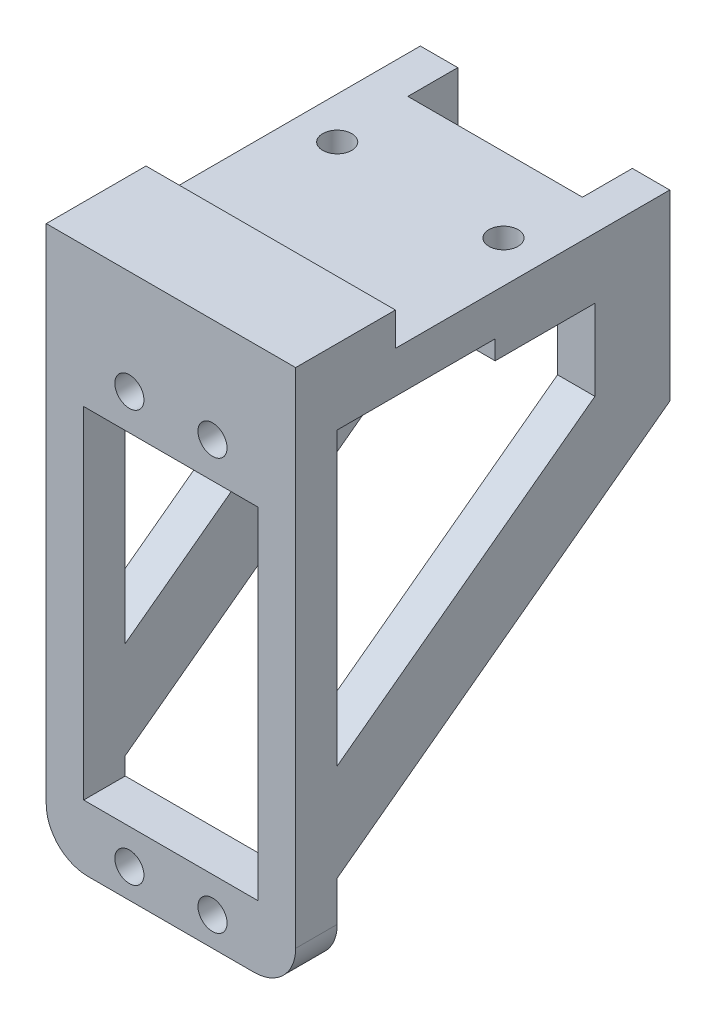
SolidWorks part; units mm, degrees
ref_plane "正面(Front)" through (0, 0, 0) normal (0, 0, 1) x (1, 0, 0)
ref_plane "平面(Top)" through (0, 0, 0) normal (0, 1, 0) x (1, 0, 0)
ref_plane "右側面(Right)" through (0, 0, 0) normal (1, 0, 0) x (0, 0, -1)
sketch "ｽｹｯﾁ1" plane through (0, 0, 0) normal (0, 0, 1) x (1, 0, 0)
  line L1 (0, 0) -> (30, 0)
  line L2 (0, 0) -> (0, 61.5)
  line L3 (0, 61.5) -> (30, 61.5)
  line L4 (30, 0) -> (30, 61.5)
  dimension "D1" = 30
  dimension "D2" = 61.5
extrude "ﾎﾞｽ - 押し出し1" add sketch "ｽｹｯﾁ1" along normal blind 5
sketch "ｽｹｯﾁ2" plane through (0, 0, 5) normal (0, 0, 1) x (1, 0, 0)
  line L0 (15, 0) -> (15, 69.5246) construction
  line L1 (0, 0) -> (30, 0) construction
  line L2 (15, 28.2) -> (37.391, 28.2) construction
  line L3 (4.5, 48.7) -> (25.5, 48.7)
  line L4 (4.5, 48.7) -> (4.5, 7.7)
  line L5 (4.5, 7.7) -> (25.5, 7.7)
  line L6 (25.5, 48.7) -> (25.5, 7.7)
  line L7 (4.5, 48.7) -> (25.5, 7.7) construction
  line L8 (4.5, 7.7) -> (25.5, 48.7) construction
  line L9 (15, 18.2) -> (37.9351, 18.2) construction
  circle A0 centre (10, 3.5) radius 1.75
  circle A1 centre (20, 3.5) radius 1.75
  circle A2 centre (10, 53) radius 1.75
  circle A3 centre (20, 53) radius 1.75
  point P4 (15, 28.2)
  dimension "D1" = 5
  dimension "D3" = 14.7
  dimension "D5" = 3.5
  dimension "D7" = 3.5
  dimension "D9" = 10
  dimension "D2" = 41
  dimension "D4" = 10
  dimension "D6" = 21
  dimension "D8" = 34.8
extrude "ｶｯﾄ - 押し出し1" cut sketch "ｽｹｯﾁ2" against normal through all
sketch "ｽｹｯﾁ3" plane through (0, 61.5, 0) normal (0, 1, 0) x (1, 0, 0)
  line L0 (30, -5) -> (30, 0) construction
  line L1 (0, 0) -> (30, 0)
  line L2 (0, 0) -> (0, 40)
  line L3 (0, 40) -> (30, 40)
  line L4 (30, 0) -> (30, 40)
  dimension "D1" = 40
extrude "ﾎﾞｽ - 押し出し2" add sketch "ｽｹｯﾁ3" against normal blind 5
sketch "ｽｹｯﾁ4" plane through (0, 61.5, 0) normal (0, 1, 0) x (1, 0, 0)
  line L0 (0, 25) -> (30, 25) construction
  line L1 (0, -5) -> (0, 40) construction
  line L2 (30, -5) -> (30, 40) construction
  line L3 (15, -5) -> (15, 47.6868) construction
  line L4 (30, -5) -> (0, -5) construction
  line L5 (30, 40) -> (0, 40) construction
  circle A0 centre (5, 25) radius 1.75
  circle A1 centre (25, 25) radius 1.75
  dimension "D1" = 3.5
  dimension "D2" = 20
  dimension "D3" = 15
extrude "ｶｯﾄ - 押し出し2" cut sketch "ｽｹｯﾁ4" against normal through all
sketch "ｽｹｯﾁ5" plane through (0, 56.5, 0) normal (0, -1, 0) x (1, 0, 0)
  line L0 (15, 0) -> (15, -30.8801) construction
  line L1 (5, -28.6) -> (8.1177, -26.8)
  line L2 (8.1177, -26.8) -> (8.1177, -23.2)
  line L3 (8.1177, -23.2) -> (5, -21.4)
  line L4 (5, -21.4) -> (1.8823, -23.2)
  line L5 (1.8823, -23.2) -> (1.8823, -26.8)
  line L6 (1.8823, -26.8) -> (5, -28.6)
  line L7 (0, 0) -> (30, 0) construction
  line L8 (28.1177, -26.8) -> (25, -28.6)
  line L9 (28.1177, -23.2) -> (28.1177, -26.8)
  line L10 (25, -21.4) -> (28.1177, -23.2)
  line L11 (21.8823, -23.2) -> (25, -21.4)
  line L12 (21.8823, -26.8) -> (21.8823, -23.2)
  line L13 (25, -28.6) -> (21.8823, -26.8)
  line L14 (0, -40) -> (0, 0) construction
  line L15 (10, -19) -> (0, -19)
  line L16 (10, -19) -> (10, -31)
  line L17 (10, -31) -> (0, -31)
  line L18 (0, -19) -> (0, -31)
  line L19 (10, -19) -> (0, -31) construction
  line L20 (10, -31) -> (0, -19) construction
  line L21 (20, -31) -> (30, -31)
  line L22 (30, -19) -> (30, -31)
  line L23 (20, -19) -> (30, -19)
  line L24 (20, -19) -> (20, -31)
  circle A0 centre (5, -25) radius 3.1177 construction
  dimension "D1" = 7.2
  dimension "D2" = 12
extrude "ﾎﾞｽ - 押し出し3" add sketch "ｽｹｯﾁ5" along normal blind 2.3
sketch "ｽｹｯﾁ6" plane through (0, 61.5, 0) normal (0, 1, 0) x (1, 0, 0)
  line L0 (30, -5) -> (30, 40) construction
  line L1 (0, -5) -> (30, -5)
  line L2 (0, -5) -> (0, 7)
  line L3 (0, 7) -> (30, 7)
  line L4 (30, -5) -> (30, 7)
  dimension "D1" = 12
extrude "ﾎﾞｽ - 押し出し4" add sketch "ｽｹｯﾁ6" along normal blind 4
sketch "ｽｹｯﾁ7" plane through (30, 0, 0) normal (1, 0, 0) x (0, 0, -1)
  line L0 (40, 56.5) -> (40, 39.5)
  line L1 (40, 39.5) -> (0, 9.8226)
  line L2 (0, 0) -> (0, 56.5) construction
  line L3 (0, 9.8226) -> (0, 21.5)
  line L4 (0, 21.5) -> (31, 44.5)
  line L5 (31, 44.5) -> (31, 56.5)
  line L6 (31, 56.5) -> (40, 56.5)
  line L7 (0, 56.5) -> (19, 56.5) construction
  dimension "D1" = 17
  dimension "D2" = 12
  dimension "D3" = 35
extrude "ﾎﾞｽ - 押し出し5" add sketch "ｽｹｯﾁ7" against normal blind 4.5
ref_plane "平面1" through (15, 0, 0) normal (-1, 0, 0) x (0, 0, 1)
mirror "ﾐﾗｰ1" about plane through (15, 0, 0) normal (-1, 0, 0) of "ﾎﾞｽ - 押し出し5"
fillet "ﾌｨﾚｯﾄ1" radius 5 2 edges at (0, 0, 2.5) (30, 0, 2.5)
sketch "ｽｹｯﾁ8" plane through (0, 56.5, 0) normal (0, -1, 0) x (1, 0, 0)
  line L0 (25.5, -40) -> (25.5, -31) construction
  line L1 (4.5, -40) -> (25.5, -40)
  line L2 (4.5, -40) -> (4.5, -34)
  line L3 (4.5, -34) -> (25.5, -34)
  line L4 (25.5, -40) -> (25.5, -34)
  dimension "D1" = 6
extrude "ｶｯﾄ - 押し出し3" cut sketch "ｽｹｯﾁ8" against normal through all
